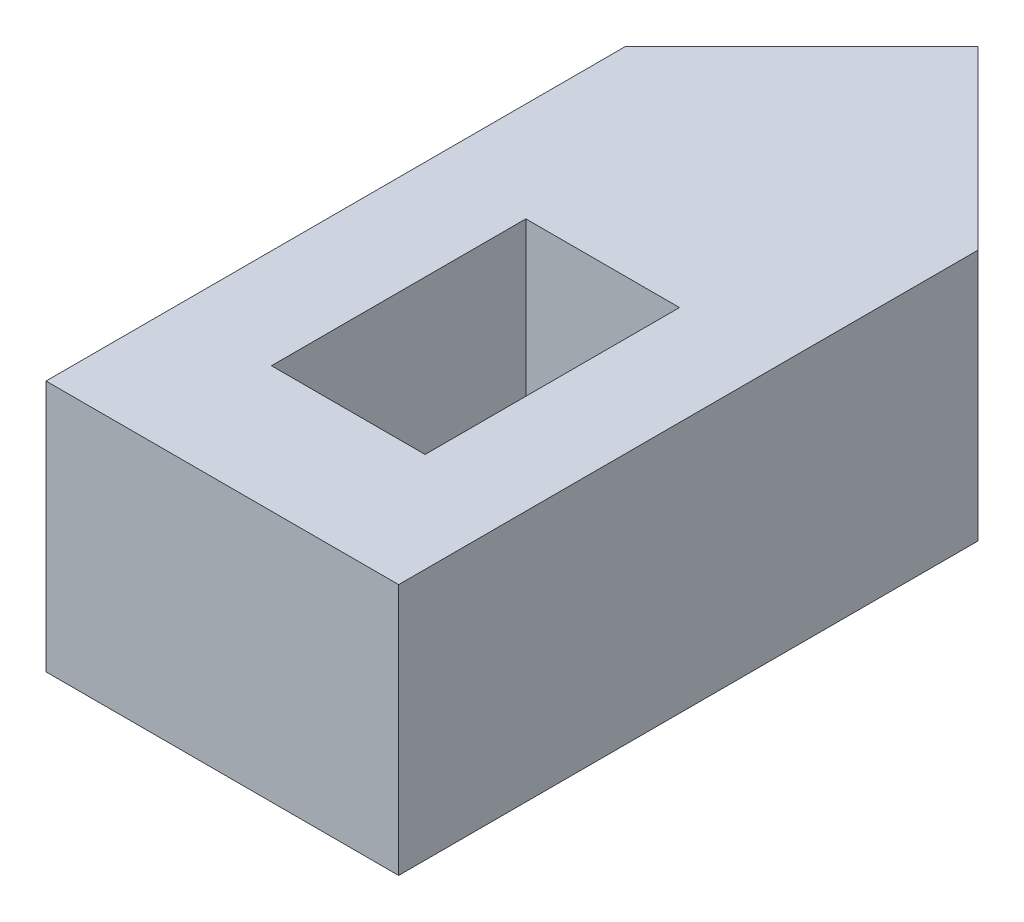
SolidWorks part; units mm, degrees
ref_plane "Front Plane" through (0, 0, 0) normal (0, 0, 1) x (1, 0, 0)
ref_plane "Top Plane" through (0, 0, 0) normal (0, 1, 0) x (1, 0, 0)
ref_plane "Right Plane" through (0, 0, 0) normal (1, 0, 0) x (0, 0, -1)
sketch "Sketch2" plane through (0, 0, 0) normal (0, 1, 0) x (1, 0, 0)
  line L1 (0, 0) -> (7, 0)
  line L2 (0, 0) -> (0, 15)
  line L3 (0, 15) -> (7, 15)
  line L4 (7, 0) -> (7, 15)
  line L5 (1.975, 2.5) -> (5.025, 2.5)
  line L6 (1.975, 2.5) -> (1.975, 7.55)
  line L7 (1.975, 7.55) -> (5.025, 7.55)
  line L8 (5.025, 2.5) -> (5.025, 7.55)
  dimension "D1" = 7
  dimension "D2" = 3.05
  dimension "D3" = 5.05
  dimension "D4" = 15
  dimension "D5" = 1.975
  dimension "D6" = 2.5
extrude "Boss-Extrude1" add sketch "Sketch2" along normal blind 5
chamfer "Chamfer1" distance 3.5 angle 45 2 edges at (0, 2.5, -15) (7, 2.5, -15)
equation "\"length\"= 15"
equation "\"width\"= 7"
equation "\"hole_length\"= 5.05"
equation "\"hole_width\"= 3.05"
equation "\"D2@Sketch2\"=\"hole_width\""
equation "\"D3@Sketch2\"=\"hole_length\""
equation "\"D1@Sketch2\"=\"width\""
equation "\"D4@Sketch2\"=\"length\""
equation "\"D5@Sketch2\"=(\"width\"-\"hole_width\")/2"
equation "\"D1@Chamfer1\"=\"width\"/2"
